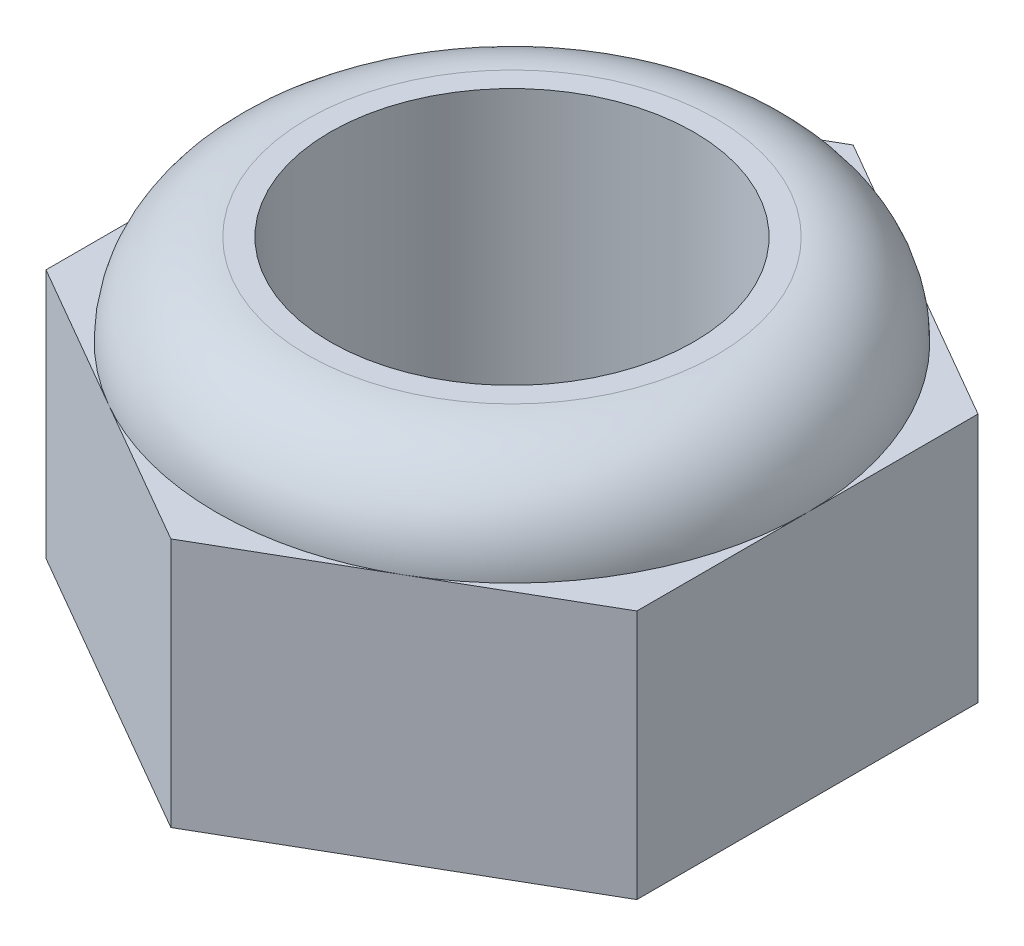
SolidWorks part; units mm, degrees
ref_plane "Front Plane" through (0, 0, 0) normal (0, 0, 1) x (1, 0, 0)
ref_plane "Top Plane" through (0, 0, 0) normal (0, 1, 0) x (1, 0, 0)
ref_plane "Right Plane" through (0, 0, 0) normal (1, 0, 0) x (0, 0, -1)
sketch "Sketch1" plane through (0, 0, 0) normal (0, 1, 0) x (1, 0, 0)
  line L1 (6.5, -3.7528) -> (6.5, 3.7528)
  line L2 (6.5, 3.7528) -> (0, 7.5056)
  line L3 (0, 7.5056) -> (-6.5, 3.7528)
  line L4 (-6.5, 3.7528) -> (-6.5, -3.7528)
  line L5 (-6.5, -3.7528) -> (0, -7.5056)
  line L6 (0, -7.5056) -> (6.5, -3.7528)
  circle A0 centre (0, 0) radius 6.5 construction
  circle A1 centre (0, 0) radius 4
  dimension "D1" = 8
  dimension "D2" = 13
extrude "Boss-Extrude1" add sketch "Sketch1" along normal blind 5.5
sketch "Sketch2" plane through (0, 5.5, 0) normal (0, 1, 0) x (1, 0, 0)
  line L0 (6.5, -3.7528) -> (6.5, 3.7528) construction
  circle A0 centre (0, 0) radius 6.5
  circle A1 centre (0, 0) radius 4
  circle A2 centre (0, 0) radius 4 construction
extrude "Boss-Extrude2" add sketch "Sketch2" along normal blind 2
fillet "Fillet1" radius 2 1 edges at (0, 7.5, 6.5)
